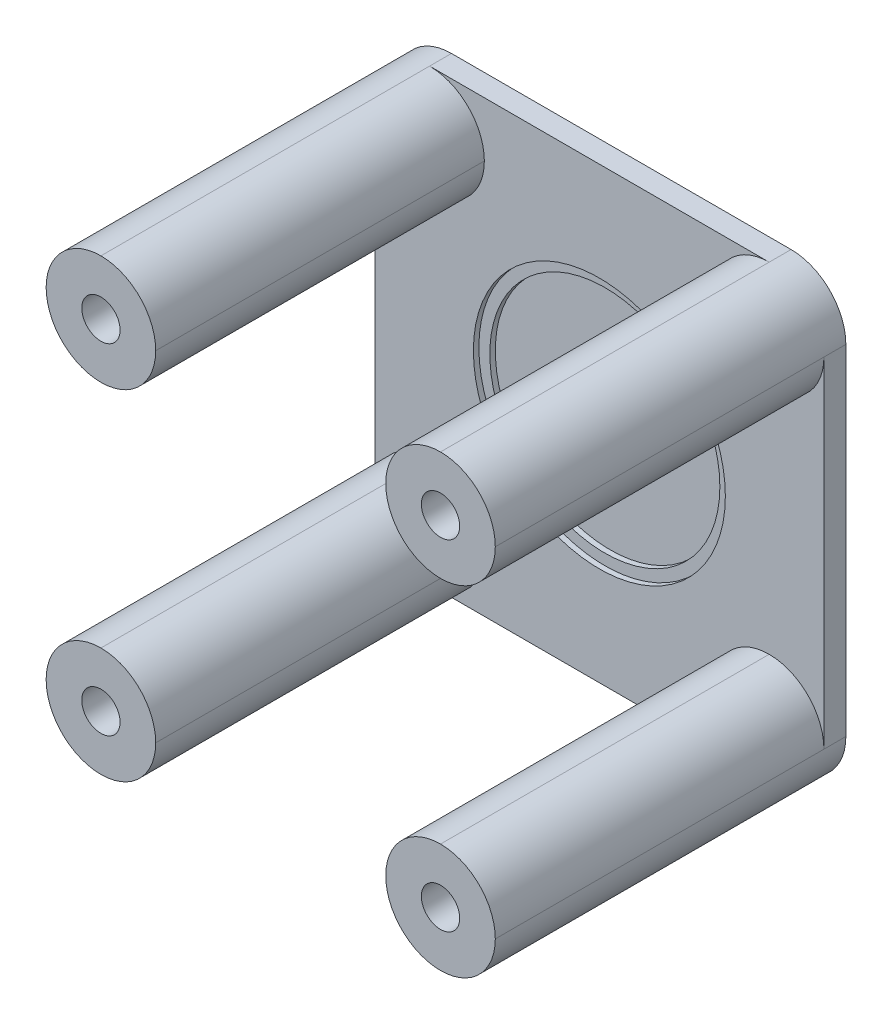
SolidWorks part; units mm, degrees
ref_plane "Front Plane" through (0, 0, 0) normal (0, 0, 1) x (1, 0, 0)
ref_plane "Top Plane" through (0, 0, 0) normal (0, 1, 0) x (1, 0, 0)
ref_plane "Right Plane" through (0, 0, 0) normal (1, 0, 0) x (0, 0, -1)
sketch "Sketch1" plane through (0, 0, 0) normal (0, 0, 1) x (1, 0, 0)
  line L0 (-55.0083, 19.8562) -> (-14.0083, 19.8562) construction
  line L1 (-55.0083, 24.8562) -> (-14.0083, 24.8562)
  line L2 (-55.0083, 24.8562) -> (-55.0083, -16.1438)
  line L3 (-55.0083, -16.1438) -> (-14.0083, -16.1438)
  line L4 (-14.0083, 24.8562) -> (-14.0083, -16.1438)
  line L5 (-50.0083, 24.8562) -> (-50.0083, -16.1438) construction
  line L6 (-55.0083, -11.1438) -> (-14.0083, -11.1438) construction
  line L7 (-19.0083, 24.8562) -> (-19.0083, -16.1438) construction
  line L8 (-55.0083, 24.8562) -> (-14.0083, -16.1438) construction
  line L9 (-55.0083, -16.1438) -> (-14.0083, 24.8562) construction
  circle A0 centre (-50.0083, 19.8562) radius 1.75
  circle A1 centre (-50.0083, -11.1438) radius 1.75
  circle A2 centre (-19.0083, -11.1438) radius 1.75
  circle A3 centre (-19.0083, 19.8562) radius 1.75
  circle A4 centre (-34.5083, 4.3562) radius 1.25
  dimension "D1" = 41
  dimension "D2" = 41
  dimension "D3" = 5
  dimension "D4" = 5
  dimension "D5" = 5
  dimension "D6" = 5
extrude "Boss-Extrude1" add sketch "Sketch1" along normal blind 2
sketch "Sketch2" plane through (0, 0, 2) normal (0, 0, 1) x (1, 0, 0)
  line L1 (-55.0083, 24.8562) -> (-45.0083, 24.8562)
  line L2 (-55.0083, 24.8562) -> (-55.0083, 14.8562)
  line L3 (-55.0083, 14.8562) -> (-45.0083, 14.8562)
  line L4 (-45.0083, 24.8562) -> (-45.0083, 14.8562)
  line L5 (-55.0083, -16.1438) -> (-45.0083, -16.1438)
  line L6 (-55.0083, -16.1438) -> (-55.0083, -6.1438)
  line L7 (-55.0083, -6.1438) -> (-45.0083, -6.1438)
  line L8 (-45.0083, -16.1438) -> (-45.0083, -6.1438)
  line L9 (-14.0083, -16.1438) -> (-24.0083, -16.1438)
  line L10 (-14.0083, -16.1438) -> (-14.0083, -6.1438)
  line L11 (-14.0083, -6.1438) -> (-24.0083, -6.1438)
  line L12 (-24.0083, -16.1438) -> (-24.0083, -6.1438)
  line L13 (-14.0083, 24.8562) -> (-24.0083, 24.8562)
  line L14 (-14.0083, 24.8562) -> (-14.0083, 14.8562)
  line L15 (-14.0083, 14.8562) -> (-24.0083, 14.8562)
  line L16 (-24.0083, 24.8562) -> (-24.0083, 14.8562)
  circle A0 centre (-50.0083, 19.8562) radius 1.75
  circle A1 centre (-50.0083, -11.1438) radius 1.75
  circle A2 centre (-19.0083, -11.1438) radius 1.75
  circle A3 centre (-19.0083, 19.8562) radius 1.75
  dimension "D1" = 10
  dimension "D2" = 10
  dimension "D3" = 10
  dimension "D4" = 10
  dimension "D5" = 10
  dimension "D6" = 10
  dimension "D7" = 10
  dimension "D8" = 10
extrude "Boss-Extrude2" add sketch "Sketch2" along normal blind 30
fillet "Fillet1" radius 5 16 edges at (-24.0083, 24.8562, 17) (-24.0083, -6.1438, 17) (-55.0083, -6.1438, 17) (-55.0083, 14.8562, 17) (-45.0083, 24.8562, 17) (-45.0083, -6.1438, 17) (-45.0083, -16.1438, 17) (-24.0083, -16.1438, 17) (-14.0083, -6.1438, 17) (-14.0083, 14.8562, 17) (-24.0083, 14.8562, 17) (-45.0083, 14.8562, 17) (-14.0083, -16.1438, 16) (-14.0083, 24.8562, 16) (-55.0083, -16.1438, 16) (-55.0083, 24.8562, 16)
sketch "Sketch3" plane through (0, 0, 2) normal (0, 0, 1) x (1, 0, 0)
  circle A1 centre (-34.5083, 4.3562) radius 10.5
extrude "Cut-Extrude1" cut sketch "Sketch3" against normal blind 1
sketch "Sketch4" plane through (0, 0, 2) normal (0, 0, 1) x (1, 0, 0)
  circle A0 centre (-34.5083, 4.3562) radius 11.5
extrude "Cut-Extrude2" cut sketch "Sketch4" against normal blind 0.5
